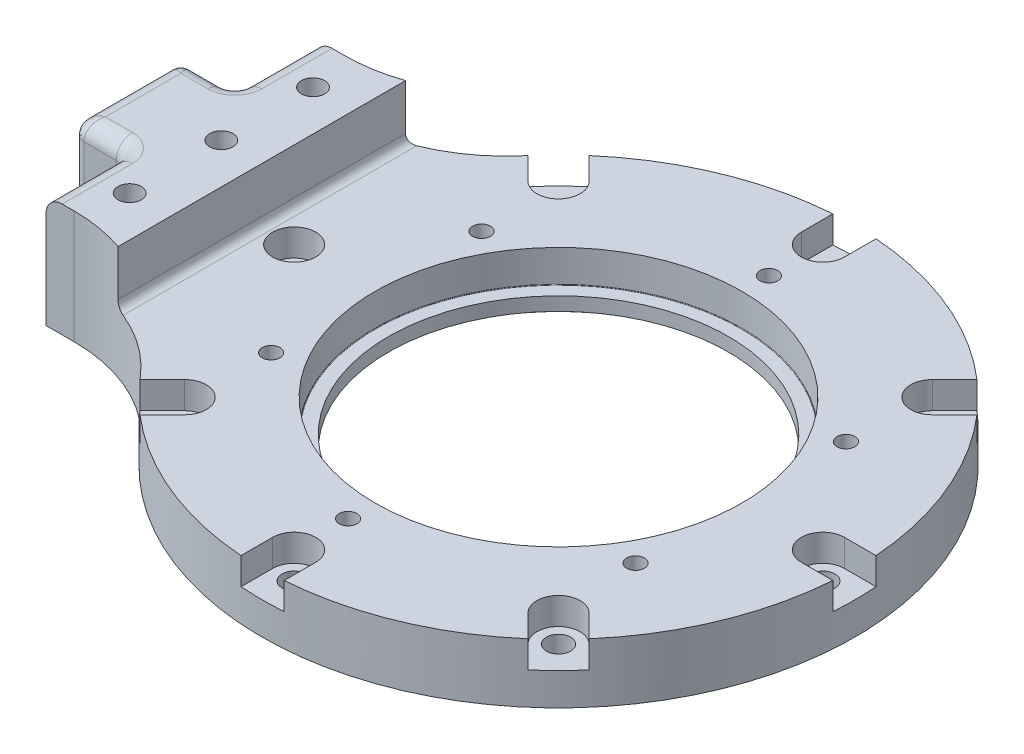
SolidWorks part; units mm, degrees
material "7075-T6, 플레이트 (SS)"
ref_plane "정면" through (0, 0, 0) normal (0, 0, 1) x (1, 0, 0)
ref_plane "윗면" through (0, 0, 0) normal (0, 1, 0) x (1, 0, 0)
ref_plane "우측면" through (0, 0, 0) normal (1, 0, 0) x (0, 0, -1)
sketch "스케치1" plane through (0, 0, 0) normal (0, 1, 0) x (1, 0, 0)
  line L1 (0, -55) -> (-70, -55)
  line L3 (0, 55) -> (-70, 55)
  line L4 (-70, -55) -> (-70, 55)
  line L5 (43.2475, -33.9802) -> (-70, 55) construction
  line L6 (43.2475, 33.9802) -> (-70, -55) construction
  arc A0 (0, -55) -> (0, 55) centre (0, 0) ccw
  circle A2 centre (0, 0) radius 35
  point P9 (0, 0)
  point P10 (0, 0)
  dimension "D1" = 110
  dimension "D4" = 70
  dimension "D5" = 70
extrude "보스-돌출1" add sketch "스케치1" along normal blind 2.5
sketch "스케치2" plane through (0, 2.5, 0) normal (0, 1, 0) x (1, 0, 0)
  line L0 (-70, 55) -> (-70, -55) construction
  line L1 (-70, -55) -> (0, -55) construction
  line L2 (0, 55) -> (-70, 55) construction
  line L3 (-70, 55) -> (-70, -55)
  line L4 (-70, -55) -> (0, -55)
  line L5 (0, 55) -> (-70, 55)
  circle A0 centre (0, 0) radius 31.5
  arc A1 (0, -55) -> (0, 55) centre (0, 0) ccw construction
  arc A2 (0, -55) -> (0, 55) centre (0, 0) ccw
  dimension "D1" = 63
extrude "보스-돌출2" add sketch "스케치2" along normal blind 2.5
sketch "스케치3" plane through (0, 5, 0) normal (0, 1, 0) x (1, 0, 0)
  line L0 (-70, 55) -> (-70, -55) construction
  line L1 (-70, -55) -> (0, -55) construction
  line L2 (0, 55) -> (-70, 55) construction
  line L3 (-70, 55) -> (-70, -55)
  line L4 (-70, -55) -> (0, -55)
  line L5 (0, 55) -> (-70, 55)
  circle A0 centre (0, 0) radius 34
  arc A1 (0, -55) -> (0, 55) centre (0, 0) ccw construction
  arc A2 (0, -55) -> (0, 55) centre (0, 0) ccw
  dimension "D1" = 68
extrude "보스-돌출3" add sketch "스케치3" along normal blind 6
sketch "스케치5" plane through (0, 11, 0) normal (0, 1, 0) x (1, 0, 0)
  circle A0 centre (0, 0) radius 49 construction
  circle A1 centre (0, 0) radius 39 construction
  point P4 (0, 39)
  point P5 (0, 49)
  dimension "D1" = 98
  dimension "D2" = 78
hole_wizard "M4 육각 소켓 머리 캡 나사용 카운터보어1" positions "스케치6" profile "스케치8" counterbore size "M4" standard "ISO" end condition through all
sketch "스케치6" plane through (0, 11, 0) normal (0, 1, 0) x (1, 0, 0)
  point P0 (0, 49)
sketch "스케치8" plane through (0, 11, -49) normal (1, 0, 0) x (0, 0, 1)
  line L0 (0, 0) -> (0, 11)
  line L1 (0, 11) -> (2.25, 11)
  line L3 (2.25, 11) -> (2.25, 5)
  line L4 (2.25, 5) -> (4, 5)
  line L5 (4, 5) -> (4, 0)
  line L7 (4, 0) -> (0, 0)
  line L11 (0, -6.35) -> (0, 107.95) construction
  dimension "관통 구멍 지름" = 4.5
  dimension "관통 구멍 깊이" = 11
  dimension "카운터보어 지름" = 8
  dimension "카운터보어 깊이" = 5
hole_wizard "M4 탭을 위한 탭 드릴1" positions "스케치9" profile "스케치10" hole size "M4" standard "ISO" end condition through all
sketch "스케치9" plane through (0, 11, 0) normal (0, 1, 0) x (1, 0, 0)
  point P0 (0, 39)
sketch "스케치10" plane through (0, 11, -39) normal (1, 0, 0) x (0, 0, 1)
  line L0 (0, 0) -> (0, 11)
  line L1 (0, 11) -> (1.65, 11)
  line L2 (1.65, 11) -> (1.65, 0)
  line L5 (1.65, 0) -> (0, 0)
  line L11 (0, -6.35) -> (0, 107.95) construction
  dimension "관통 구멍 지름" = 3.3
  dimension "관통 구멍 깊이" = 11
pattern_circular "원형 패턴1" count 8 over 360 about axis through (0, 2.5, 0) along (0, -1, 0) of "M4 육각 소켓 머리 캡 나사용 카운터보어1"
pattern_circular "원형 패턴2" count 6 over 360 about axis through (0, 2.5, 0) along (0, -1, 0) of "M4 탭을 위한 탭 드릴1" reverse direction yes
sketch "스케치11" plane through (0, 11, 0) normal (0, 1, 0) x (1, 0, 0)
  line L1 (4, 61) -> (-4, 61)
  line L2 (4, 61) -> (4, 49)
  line L3 (4, 49) -> (-4, 49)
  line L4 (-4, 61) -> (-4, 49)
  line L5 (4, 61) -> (-4, 49) construction
  line L6 (4, 49) -> (-4, 61) construction
  circle A2 centre (0, 49) radius 4 construction
  circle A3 centre (0, 49) radius 4 construction
  point P0 (0, 55)
extrude "컷-돌출1" cut sketch "스케치11" against normal mid plane 10
sketch "스케치12" plane through (0, 11, 0) normal (0, 1, 0) x (1, 0, 0)
  line L5 (-70, 55) -> (-70, -55) construction
  line L6 (-70, -25) -> (-55, -25)
  line L7 (-70, -25) -> (-70, 25)
  line L8 (-70, 25) -> (-55, 25)
  line L9 (-55, -25) -> (-55, 25)
  line L10 (-70, -55) -> (0, -55) construction
  line L11 (-4, 55) -> (-70, 55) construction
  dimension "D1" = 15
  dimension "D2" = 30
  dimension "D3" = 30
extrude "보스-돌출4" add sketch "스케치12" along normal blind 10
sketch "스케치13" plane through (0, 11, 0) normal (0, 1, 0) x (1, 0, 0)
  line L1 (-70, -25) -> (-48.9898, -25)
  line L2 (-70, -25) -> (-70, 25)
  line L3 (-70, 25) -> (-48.9898, 25)
  line L5 (100, -65) -> (-100, -65)
  line L6 (100, -65) -> (100, 65)
  line L7 (100, 65) -> (-100, 65)
  line L8 (-100, -65) -> (-100, 65)
  line L9 (100, -65) -> (-100, 65) construction
  line L10 (100, 65) -> (-100, -65) construction
  arc A0 (-48.9898, -25) -> (-48.9898, 25) centre (0, 0) ccw
  dimension "D1" = 110
  dimension "D2" = 70
  dimension "D3" = 200
  dimension "D4" = 25
  dimension "D5" = 25
  dimension "D6" = 130
extrude "컷-돌출2" cut sketch "스케치13" against normal through all
pattern_circular "원형 패턴3" count 8 over 360 about axis through (0, 2.5, 0) along (0, -1, 0) skipping 2 of "컷-돌출1" reverse direction yes
fillet "필렛1" radius 0.1 2 edges at (0, 5, 34) (0, 2.5, 35)
fillet "필렛2" radius 1.5 1 edges at (-55, 11, 0)
sketch "스케치14" plane through (-70, 0, 0) normal (-1, 0, 0) x (0, 0, 1)
  line L0 (-25, 21) -> (25, 21) construction
  line L1 (-10, 0) -> (10, 0)
  line L2 (-10, 0) -> (-10, 21)
  line L3 (-10, 21) -> (10, 21)
  line L4 (10, 0) -> (10, 21)
  line L5 (-10, 0) -> (10, 21) construction
  line L6 (-10, 21) -> (10, 0) construction
  line L7 (-25, 0) -> (25, 0) construction
  point P0 (0, 10.5)
  dimension "D1" = 20
extrude "보스-돌출5" add sketch "스케치14" along normal blind 10
fillet "필렛5" radius 2 2 edges at (-70, 10.5, 10) (-70, 10.5, -10)
fillet "필렛6" radius 2 2 edges at (-80, 10.5, -10) (-80, 10.5, 10)
fillet "필렛7" radius 3 9 edges at (-70, 21, 18.5) (-70.5858, 21, 10.5858) (-79.4142, 21, 9.4142) (-80, 21, 0) (-79.4142, 21, -9.4142) (-70, 21, -18.5) (-70.5858, 21, -10.5858) (-75, 21, 10) (-75, 21, -10)
sketch "스케치17" plane through (0, 0, 0) normal (0, -1, 0) x (1, 0, 0)
  line L0 (-70, 12) -> (-70, 25) construction
  point P0 (-62.5, 0)
  point P3 (0, 0)
  dimension "D1" = 7.5
hole_wizard "M4 육각 소켓 머리 캡 나사용 카운터보어2" positions "스케치18" profile "스케치19" counterbore size "M4" standard "ISO" end condition through all
sketch "스케치18" plane through (0, 0, 0) normal (0, -1, 0) x (-1, 0, 0)
  point P0 (62.5, 0)
sketch "스케치19" plane through (-62.5, 0, 0) normal (1, 0, 0) x (0, 0, -1)
  line L0 (0, 0) -> (0, 21)
  line L1 (0, 21) -> (2.15, 21)
  line L3 (2.15, 21) -> (2.15, 16)
  line L4 (2.15, 16) -> (4, 16)
  line L5 (4, 16) -> (4, 0)
  line L7 (4, 0) -> (0, 0)
  line L11 (0, -6.35) -> (0, 107.95) construction
  dimension "관통 구멍 지름" = 4.3
  dimension "관통 구멍 깊이" = 21
  dimension "카운터보어 지름" = 8
  dimension "카운터보어 깊이" = 16
pattern_linear "선형 패턴2" count 2 spacing 17 along (0, 0, -1) count 2 spacing 17 along (0, 0, 1) of "M4 육각 소켓 머리 캡 나사용 카운터보어2"
fillet "필렛8" radius 30 2 edges at (-48.9898, 5.5, 25) (-48.9898, 5.5, -25)
